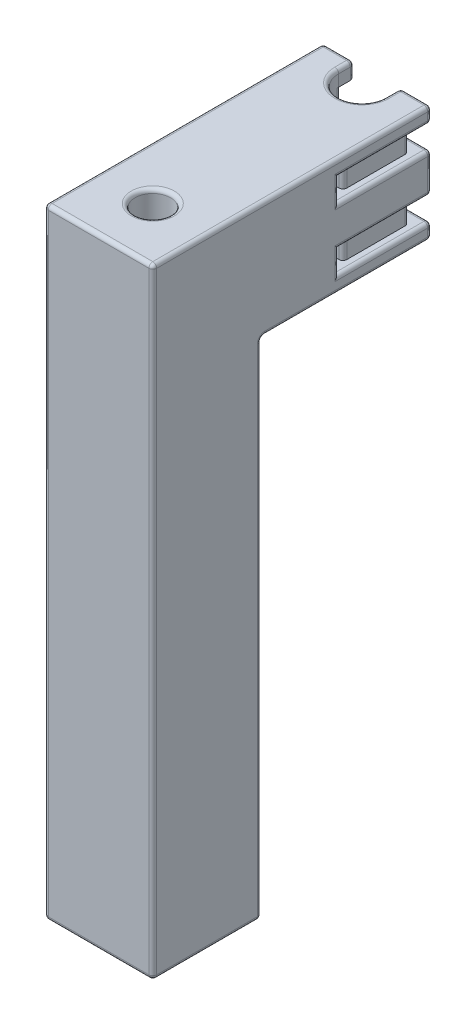
SolidWorks part; units mm, degrees
ref_plane "Front Plane" through (0, 0, 0) normal (0, 0, 1) x (1, 0, 0)
ref_plane "Top Plane" through (0, 0, 0) normal (0, 1, 0) x (1, 0, 0)
ref_plane "Right Plane" through (0, 0, 0) normal (1, 0, 0) x (0, 0, -1)
sketch "Sketch1" plane through (0, 0, 0) normal (0, 1, 0) x (1, 0, 0)
  line L0 (0, 20.9536) -> (0, -51.2812) construction
  line L1 (-31.5295, 0) -> (37.7731, 0) construction
  line L3 (-7, -34) -> (7, -34)
  line L4 (-7, -34) -> (-7, -20)
  line L5 (-7, -20) -> (7, -20)
  line L6 (7, -34) -> (7, -20)
  line L7 (-7, -34) -> (7, -20) construction
  line L8 (-7, -20) -> (7, -34) construction
  point P5 (0, -27)
  dimension "D1" = 14
  dimension "D2" = 14
  dimension "D3" = 20
extrude "Boss-Extrude1" add sketch "Sketch1" along normal blind 65
sketch "Sketch3" plane through (0, 65, 0) normal (0, 1, 0) x (1, 0, 0)
  line L0 (0, 16.3494) -> (0, -50.3764) construction
  line L2 (-7, -34) -> (7, -34)
  line L3 (-7, -34) -> (-7, 2)
  line L4 (-7, 2) -> (7, 2)
  line L5 (7, -34) -> (7, 2)
  dimension "D1" = 14
  dimension "D2" = 36
extrude "Boss-Extrude2" add sketch "Sketch3" along normal blind 15
sketch "Sketch4" plane through (0, 80, 0) normal (0, 1, 0) x (1, 0, 0)
  line L0 (-7.8841, 0) -> (8.2056, 0) construction
  line L1 (-3, 0) -> (-3, 2)
  line L2 (7, 2) -> (-7, 2) construction
  line L3 (3, 0) -> (3, 2)
  line L4 (3, 2) -> (-3, 2)
  arc A0 (-3, 0) -> (3, 0) centre (0, 0) ccw
  dimension "D1" = 6
extrude "Cut-Extrude1" cut sketch "Sketch4" against normal through all both and the other way through all
sketch "Sketch5" plane through (7, 0, 0) normal (1, 0, 0) x (0, 0, -1)
  line L0 (2, 80) -> (2, 65) construction
  line L1 (2, 78) -> (0.25, 78)
  line L2 (2, 78) -> (2, 75)
  line L3 (2, 75) -> (0.25, 75)
  line L4 (0.25, 78) -> (0.25, 75)
  line L5 (-34, 80) -> (2, 80) construction
  line L6 (-38.989, 72.5) -> (15.3579, 72.5) construction
  line L7 (0.25, 67) -> (0.25, 70)
  line L8 (2, 67) -> (2, 70)
  line L9 (2, 70) -> (0.25, 70)
  line L10 (2, 67) -> (0.25, 67)
  line L11 (-4, 39.6976) -> (-4, 16.0859) construction
  line L13 (-8.25, 67) -> (-8.25, 70)
  line L14 (-10, 67) -> (-8.25, 67)
  line L15 (-10, 67) -> (-10, 70)
  line L16 (-10, 70) -> (-8.25, 70)
  line L17 (-8.25, 78) -> (-8.25, 75)
  line L18 (-10, 75) -> (-8.25, 75)
  line L19 (-10, 78) -> (-10, 75)
  line L20 (-10, 78) -> (-8.25, 78)
  point P10 (2, 72.5)
  dimension "D1" = 3
  dimension "D2" = 1.75
  dimension "D3" = 2
  dimension "D4" = 6
extrude "Cut-Extrude2" cut sketch "Sketch5" against normal through all both
sketch "Sketch6" plane through (0, 0, -0.25) normal (0, 0, -1) x (-1, 0, 0)
  line L0 (-3, 75) -> (-7, 75) construction
  line L1 (-7, 78) -> (-5.8, 78)
  line L2 (-7, 78) -> (-7, 75)
  line L3 (-7, 75) -> (-5.8, 75)
  line L4 (-5.8, 78) -> (-5.8, 75)
  line L5 (0, 37.0199) -> (0, -11.7144) construction
  line L6 (7, 75) -> (5.8, 75)
  line L7 (5.8, 78) -> (5.8, 75)
  line L8 (7, 78) -> (5.8, 78)
  line L9 (7, 78) -> (7, 75)
  line L10 (-7, 70) -> (-7, 67) construction
  line L11 (-7, 70) -> (-5.8, 70)
  line L12 (-7, 70) -> (-7, 67)
  line L13 (-7, 67) -> (-5.8, 67)
  line L14 (-5.8, 70) -> (-5.8, 67)
  line L15 (-3, 70) -> (-7, 70) construction
  line L16 (-3, 67) -> (-7, 67) construction
  line L17 (7, 70) -> (7, 67)
  line L18 (7, 67) -> (5.8, 67)
  line L19 (5.8, 70) -> (5.8, 67)
  line L20 (7, 70) -> (5.8, 70)
  dimension "D1" = 1.2
  dimension "D2" = 1.2
extrude "Cut-Extrude3" cut sketch "Sketch6" against normal up to next
sketch "Sketch7" plane through (0, 0, 0) normal (0, -1, 0) x (1, 0, 0)
  line L0 (0, 34.6651) -> (0, 17.8755) construction
  line L1 (-8.4882, 27) -> (8.1753, 27) construction
  line L2 (7, 34) -> (7, 20) construction
  circle A1 centre (0, 27) radius 3.175
  point P7 (7, 27)
  dimension "D1" = 6.35
extrude "Cut-Extrude4" cut sketch "Sketch7" against normal blind 4.699
sketch "Sketch8" plane through (0, 4.699, 0) normal (0, -1, 0) x (1, 0, 0)
  circle A0 centre (0, 27) radius 2.286
  dimension "D1" = 4.572
extrude "Cut-Extrude5" cut sketch "Sketch8" against normal through all
fillet "Fillet1" radius 0.5 57 edges at (-3, 66, -2) (-5, 67, -2) (5, 67, -2) (3, 66, -2) (-5, 75, -2) (-5, 70, -2) (-3, 72.5, -2) (-5, 78, -2) (-3, 79, -2) (3, 79, -2) (5, 78, -2) (5, 75, -2) (3, 72.5, -2) (5, 70, -2) (-5, 65, -2) (5, 65, -2) (3, 65, -1) (0, 65, 3) (-3, 65, -1) (0, 65, 20) (0, 0, 20) (7, 65, 9) (7, 32.5, 20) (7, 0, 27) (7, 79, -2) (7, 78, 4) (7, 76.5, 10) (7, 75, 4) (7, 72.5, -2) (7, 70, 4) (7, 68.5, 10) (7, 67, 4) (7, 66, -2) (7, 40, 34) (0, 0, 34) (-7, 76.5, 10) (-7, 78, 4) (-7, 79, -2) (-7, 40, 34) (-7, 0, 27) (-7, 32.5, 20) (-7, 65, 9) (-7, 66, -2) (-7, 67, 4) (-7, 68.5, 10) (-7, 70, 4) (-7, 72.5, -2) (-7, 75, 4) (3, 80, -1) (5, 80, -2) (7, 80, 16) (0, 80, 34) (-7, 80, 16) (-5, 80, -2) (-3, 80, -1) (0, 80, 3) (0, 80, 24.714)
draft "Draft1" type of draft neutral plane draft angle 4 faces to draft 1 face at (0, 4.699, 23.825) neutral plane through (0, 0, 0) neutral plane normal (0, -1, 0) parameters "D1"=4
fillet "Fillet2" radius 0.5 12 edges at (-5.8, 68.5, 8.25) (-5.8, 76.5, 8.25) (3, 76.5, -0.25) (3, 68.5, -0.25) (-3, 68.5, -0.25) (-3, 76.5, -0.25) (-5.8, 76.5, -0.25) (-5.8, 68.5, -0.25) (5.8, 68.5, -0.25) (5.8, 68.5, 8.25) (5.8, 76.5, 8.25) (5.8, 76.5, -0.25)
